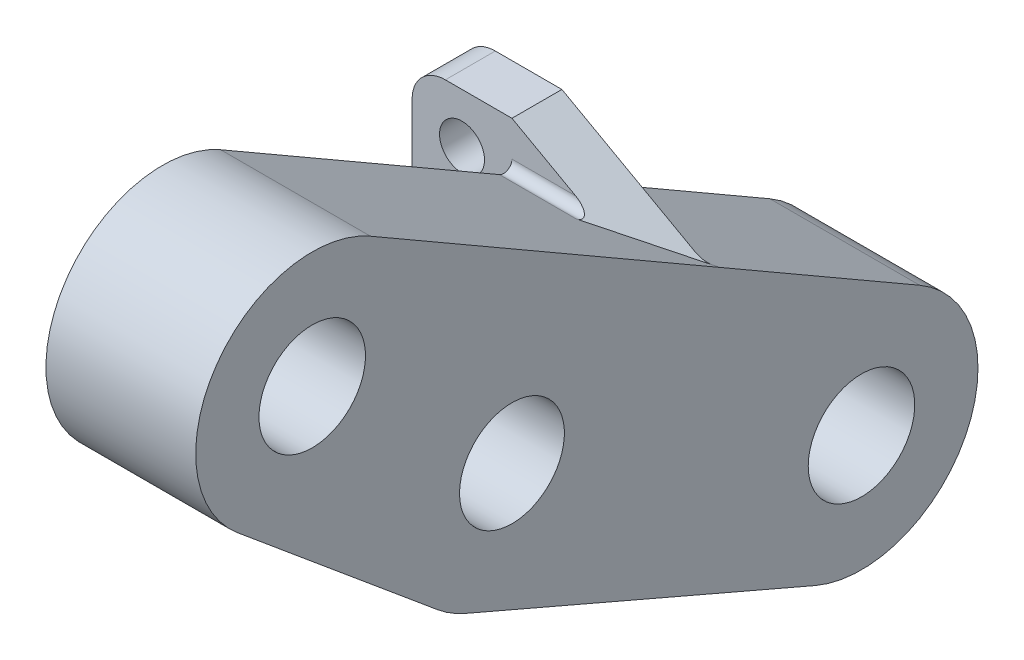
SolidWorks part; units mm, degrees
note: '?' marks a value the reader was unsure of.
ref_plane "Front Plane" through (0, 0, 0) normal (0, 0, 1) x (1, 0, 0)
ref_plane "Top Plane" through (0, 0, 0) normal (0, 1, 0) x (1, 0, 0)
ref_plane "Right Plane" through (0, 0, 0) normal (1, 0, 0) x (0, 0, -1)
ref_plane "Plane4" through (9, 0, 0) normal (1, 0, 0) x (0, 0, -1)
sketch "Sketch1" plane through (9, 0, 0) normal (1, 0, 0) x (0, 0, -1)
  line L0 (3.5235, 220.1706) -> (-29.4773, 239.2218)
  line L1 (-32.977, 233.1595) -> (-32.9759, 206.2902) construction
  line L3 (-37.4582, 227.7819) -> (-25.4578, 217.7819)
  line L4 (-23.7472, 216.7311) -> (-2.7468, 207.68)
  circle A1 centre (0.0238, 214.1083) radius 3.2
  circle A2 centre (-32.977, 233.1595) radius 3.2
  arc A3 (-2.7468, 207.68) -> (3.5235, 220.1706) centre (0.0238, 214.1083) ccw
  arc A4 (-29.4773, 239.2218) -> (-37.4582, 227.7819) centre (-32.977, 233.1595) ccw
  circle A6 centre (-20.9766, 223.1595) radius 3.15
  arc A7 (-25.4578, 217.7819) -> (-23.7472, 216.7311) centre (-20.9766, 223.1595) ccw
  dimension "D1" = 6.3
  dimension "D2" = 6.4
  dimension "D3" = 7
  dimension "D4" = 38.1051
  dimension "D5" = 60
  dimension "D6" = 12
  dimension "D7" = 10
extrude "Boss-Extrude1" add sketch "Sketch1" against normal blind 9
sketch "Sketch2" plane through (0, 0, 0) normal (-1, 0, 0) x (0, 0, 1)
  line L0 (23.7472, 216.7311) -> (2.7468, 207.68) construction
  line L1 (8.9762, 232.1083) -> (11.9762, 232.1083)
  line L2 (8.9762, 232.1083) -> (8.9762, 210.3648)
  line L3 (8.9762, 210.3648) -> (11.9762, 211.6578)
  line L4 (11.9762, 232.1083) -> (11.9762, 211.6578)
  circle A0 centre (-0.0238, 214.1083) radius 3.2 construction
  dimension "D1" = 12
  dimension "D3" = 18
  dimension "D2" = 3
extrude "Boss-Extrude2" add sketch "Sketch2" along normal blind 6 and the other way up to surface other way up to face at (9, 223.1595, 24.1266)
ref_axis "Axis1" through (0, 214.1083, -0.0238) along (1, 0, 0)?
sketch "Sketch3" plane through (0, 0, 8.9762) normal (0, 0, -1) x (-1, 0, 0)
  line L0 (0, 207.1083) -> (0, 220.1706) construction
  line L2 (0, 214.1083) -> (-9, 214.1083) construction
  circle A0 centre (3, 229.1083) radius 1.35
  dimension "D2" = 2.7
  dimension "D1" = 3
  dimension "D3" = 15
extrude "Cut-Extrude1" cut sketch "Sketch3" against normal through all
chamfer "Chamfer1" distance 6 distance2 10 1 edges at (-6, 211.0113, 10.4762)
chamfer "Chamfer2" distance 5 distance2 9 1 edges at (9, 232.1083, 10.4762)
fillet "Fillet1" radius 2 1 edges at (-6, 232.1083, 10.4762)
fillet "Fillet2" radius 0.5 1 edges at (4.2495, 227.3867, 8.9762)
fillet "Fillet3" radius 0.5 1 edges at (2.6908, 229.1186, 11.9762)
fillet "Fillet4" radius 1 1 edges at (0, 219.0201, 8.9762)
